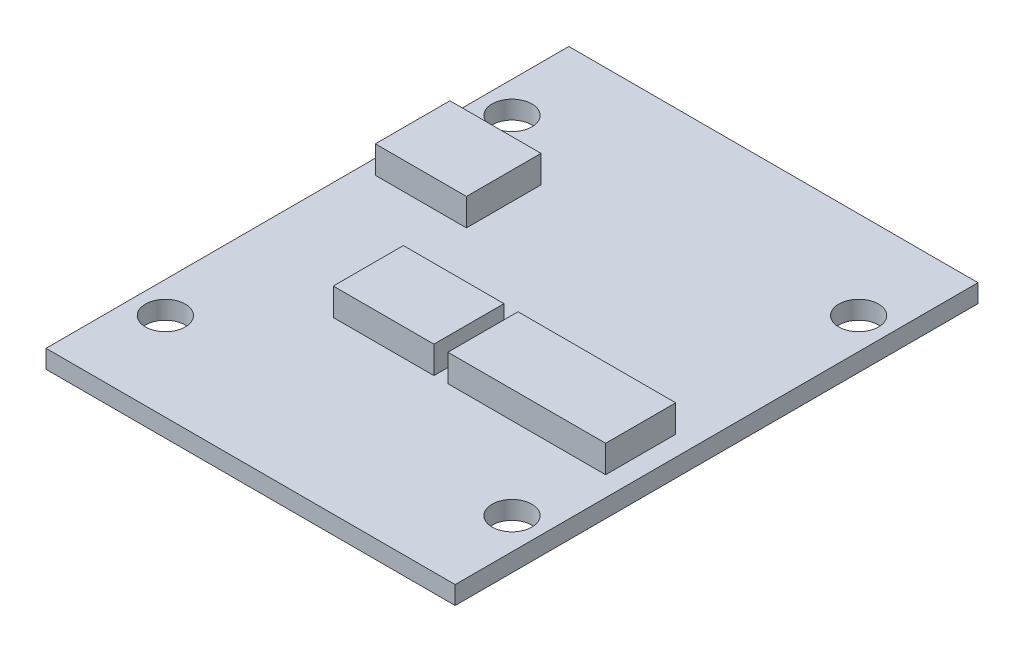
SolidWorks part; units mm, degrees
ref_plane "Front Plane" through (0, 0, 0) normal (0, 0, 1) x (1, 0, 0)
ref_plane "Top Plane" through (0, 0, 0) normal (0, 1, 0) x (1, 0, 0)
ref_plane "Right Plane" through (0, 0, 0) normal (1, 0, 0) x (0, 0, -1)
sketch "Sketch1" plane through (0, 0, 0) normal (0, 1, 0) x (1, 0, 0)
  line L0 (0, 18) -> (0, -18) construction
  line L1 (-18, 23) -> (18, 23)
  line L2 (-18, 23) -> (-18, -23)
  line L3 (-18, -23) -> (18, -23)
  line L4 (18, 23) -> (18, -23)
  line L5 (-18, 23) -> (18, -23) construction
  line L6 (-18, -23) -> (18, 23) construction
  line L7 (18, -18) -> (-18, -18)
  line L8 (18, -18) -> (18, 18)
  line L9 (18, 18) -> (-18, 18)
  line L10 (-18, -18) -> (-18, 18)
  line L11 (18, -18) -> (-18, 18) construction
  line L12 (18, 18) -> (-18, -18) construction
  line L13 (-18, 0) -> (18, 0) construction
  circle A0 centre (-15.25, 15.25) radius 1.75
  circle A1 centre (15.25, 15.25) radius 1.75
  circle A2 centre (-15.25, -15.25) radius 1.75
  circle A3 centre (15.25, -15.25) radius 1.75
  point P0 (0, 0)
  point P6 (0, 0)
  dimension "D3" = 3.5
  dimension "D1" = 46
  dimension "D2" = 36
  dimension "D4" = 30.5
extrude "PCB" add sketch "Sketch1" along normal blind 1.6 contours L9 L4 L1 L2 | L4 L9 L2 L7 A3 A1 A0 A2 | L4 L7 L2 L3 region at (0, 0, -20.5) region at (0, 0, 0) region at (0, 0, 20.5)
sketch "Sketch2" plane through (0, 1.6, 0) normal (0, 1, 0) x (1, 0, 0)
  line L1 (16.2527, -1.8499) -> (2.3784, -1.8499)
  line L2 (16.2527, -1.8499) -> (16.2527, -8.0162)
  line L3 (16.2527, -8.0162) -> (2.3784, -8.0162)
  line L4 (2.3784, -1.8499) -> (2.3784, -8.0162)
  line L5 (1.1452, -1.8499) -> (-7.7079, -1.8499)
  line L6 (1.1452, -1.8499) -> (1.1452, -8.0162)
  line L7 (1.1452, -8.0162) -> (-7.7079, -8.0162)
  line L8 (-7.7079, -1.8499) -> (-7.7079, -8.0162)
  line L9 (-16.6931, 11.2315) -> (-8.6769, 11.2315)
  line L10 (-16.6931, 11.2315) -> (-16.6931, 4.6688)
  line L11 (-16.6931, 4.6688) -> (-8.6769, 4.6688)
  line L12 (-8.6769, 11.2315) -> (-8.6769, 4.6688)
extrude "Components" add sketch "Sketch2" along normal offset from surface (2.4 mm away) 4 contours L12 L9 L10 L11 | L5 L8 L7 L6 | L1 L4 L3 L2 region at (9.3156, 1.6, 4.9331) region at (-3.2814, 1.6, 4.9331) region at (-12.685, 1.6, -7.9502) up to face at (0, 0, 0)
